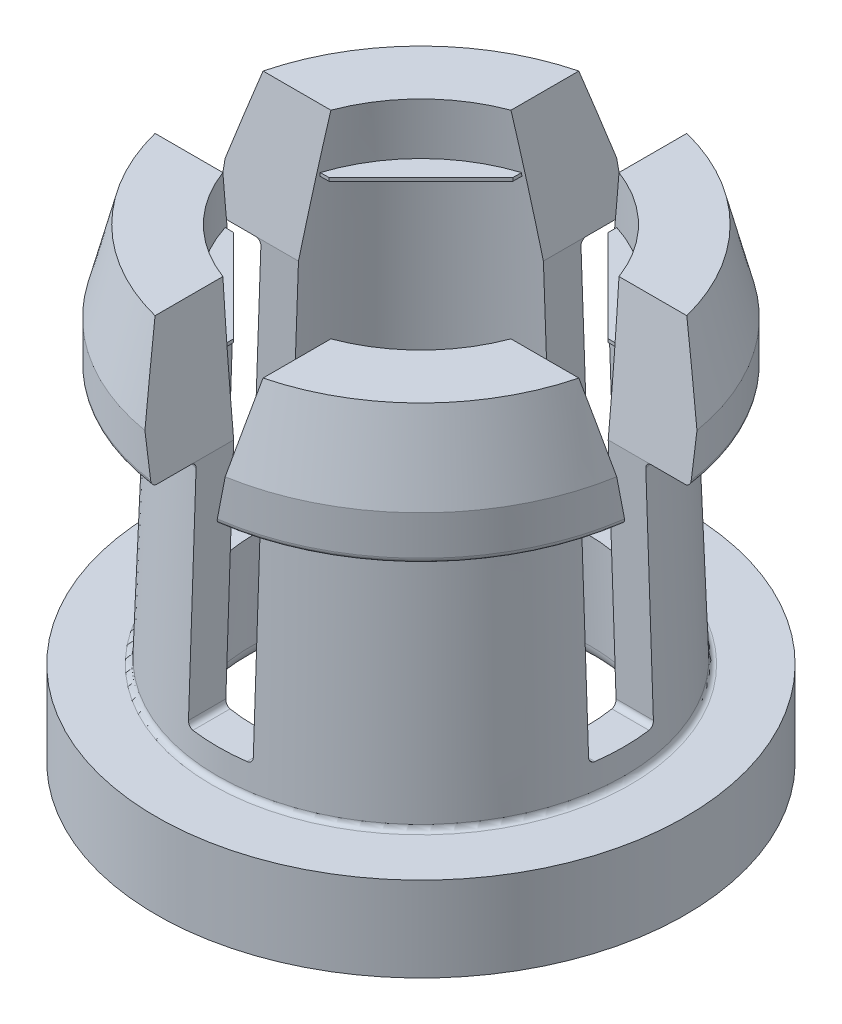
SolidWorks part; units mm, degrees
material "policarbonato"
ref_plane "Alzado" through (0, 0, 0) normal (0, 0, 1) x (1, 0, 0)
ref_plane "Planta" through (0, 0, 0) normal (0, 1, 0) x (1, 0, 0)
ref_plane "Vista lateral" through (0, 0, 0) normal (1, 0, 0) x (0, 0, -1)
sketch "Croquis1" plane through (0, 0, 0) normal (0, 0, 1) x (1, 0, 0)
  line L0 (0, 0) -> (0, 16.8439) construction
  line L2 (3.15, 0) -> (4.9, 0)
  line L3 (4.9, 0) -> (4.9, 1.57)
  line L4 (4.9, 1.57) -> (3.7756, 1.57)
  line L5 (3.7756, 1.57) -> (3.6104, 6.3)
  line L6 (3.6104, 6.3) -> (4.4309, 6.3)
  line L7 (4.4309, 6.3) -> (4.4309, 7.13)
  line L8 (4.4309, 7.13) -> (4.049, 8.62)
  line L9 (4.049, 8.62) -> (2.849, 8.62)
  line L10 (2.849, 8.62) -> (3.15, 0)
  dimension "D1" = 1.75
  dimension "D2" = 3.15
  dimension "D3" = 1.57
  dimension "D4" = 4.73
  dimension "D5" = 8.62
  dimension "D6" = 0.68
  dimension "D7" = 0.83
  dimension "D8" = 1.2
  dimension "D9" = 92
  dimension "D10" = 1.5
revolve "Revolución1" add sketch "Croquis1" angle 360 about L0
sketch "Croquis2" plane through (0, 8.62, 0) normal (0, 1, 0) x (1, 0, 0)
  line L0 (-7.7, 0) -> (-10.6462, 0) construction
  line L1 (0.6, 0.6) -> (0.6, 7.7)
  line L2 (7.7, 0) -> (9.0539, 0) construction
  line L3 (-0.6, 0.6) -> (0.6, -0.6) construction
  line L4 (-0.6, 0.6) -> (-0.6, 7.7)
  line L5 (0.6, 0.6) -> (-0.6, -0.6) construction
  line L6 (-0.6, -7.7) -> (0.6, -7.7)
  line L7 (7.7, 0.6) -> (0.6, 0.6)
  line L8 (-0.6, -7.7) -> (-0.6, -0.6)
  line L9 (-0.6, 7.7) -> (0.6, 7.7)
  line L10 (0.6, -7.7) -> (0.6, -0.6)
  line L11 (-7.7, 0.6) -> (-7.7, -0.6)
  line L12 (-7.7, -0.6) -> (-0.6, -0.6)
  line L13 (7.7, 0.6) -> (7.7, -0.6)
  line L14 (-0.6, 0.6) -> (-7.7, 0.6)
  line L15 (0.6, -0.6) -> (7.7, -0.6)
  point P17 (0, -0.6)
  point P18 (0, 0.6)
  dimension "D3" = 0.6
  dimension "D4" = 0.6
  dimension "D6" = 7.7
extrude "Cortar-Extruir1" cut sketch "Croquis2" against normal blind 6.5
sketch "Croquis3" plane through (0, 0, 0) normal (1, 0, 0) x (0, 0, -1)
  line L0 (-0.6, 6.3) -> (-1, 8.62)
  line L1 (-0.6, 8.62) -> (-4.0043, 8.62) construction
  line L2 (-1, 8.62) -> (1, 8.62)
  line L3 (4.0043, 8.62) -> (0.6, 8.62) construction
  line L4 (1, 8.62) -> (0.6, 6.3)
  line L5 (0.6, 6.3) -> (-0.6, 6.3)
  line L6 (0, 6.3) -> (0, 8.62) construction
  dimension "D1" = 2
extrude "Cortar-Extruir2" cut sketch "Croquis3" against normal through all and the other way through all
sketch "Croquis4" plane through (0, 0, 0) normal (0, 0, 1) x (1, 0, 0)
  line L0 (-0.6, 6.3) -> (-1, 8.62)
  line L1 (-0.6, 8.62) -> (-3.9236, 8.62) construction
  line L2 (-1, 8.62) -> (1, 8.62)
  line L3 (3.9236, 8.62) -> (0.6, 8.62) construction
  line L4 (1, 8.62) -> (0.6, 6.3)
  line L5 (0.6, 6.3) -> (-0.6, 6.3)
  line L6 (0, 6.3) -> (0, 8.62) construction
  dimension "D1" = 2
extrude "Cortar-Extruir3" cut sketch "Croquis4" against normal through all and the other way through all
fillet "Redondeo1" radius 0.1 17 edges at (2.5529, 6.3, -2.5529) (-2.5529, 6.3, -2.5529) (-2.5529, 6.3, 2.5529) (2.5529, 6.3, 2.5529) (0, 1.57, -3.7756) (-3.1331, 6.3, -3.1331) (3.1331, 6.3, -3.1331) (3.1331, 6.3, 3.1331) (-3.1331, 6.3, 3.1331) (-0.6, 2.12, 3.3625) (0.6, 2.12, 3.3625) (-3.3625, 2.12, -0.6) (-3.3625, 2.12, 0.6) (3.3625, 2.12, -0.6) (3.3625, 2.12, 0.6) (-0.6, 2.12, -3.3625) (0.6, 2.12, -3.3625)
sketch "Croquis5" plane through (0, 8.62, 0) normal (0, 1, 0) x (1, 0, 0)
  line L0 (-2.5851, 0.8828) -> (-0.8828, 2.5851)
  line L1 (-0.8732, 3.1601) -> (-1, 3.2956)
  line L2 (-1, 3.9236) -> (-1, 2.6677) construction
  line L3 (-1, 3.2956) -> (-3.2956, 1)
  line L4 (-3.9236, 1) -> (-2.6677, 1) construction
  line L5 (-3.2956, 1) -> (-3.1601, 0.8732)
  line L6 (-2.5851, -0.8828) -> (-0.8828, -2.5851)
  line L7 (-0.8732, -3.1601) -> (-1, -3.2956)
  line L8 (-1, -2.6677) -> (-1, -3.9236) construction
  line L9 (-1, -3.2956) -> (-3.2956, -1)
  line L10 (-3.9236, -1) -> (-2.6677, -1) construction
  line L11 (-3.2956, -1) -> (-3.1601, -0.8732)
  line L12 (0.8828, 2.5851) -> (2.5851, 0.8828)
  line L13 (3.1601, 0.8732) -> (3.2956, 1)
  line L14 (2.6677, 1) -> (3.9236, 1) construction
  line L15 (3.2956, 1) -> (1, 3.2956)
  line L16 (1, 3.9236) -> (1, 2.6677) construction
  line L17 (1, 3.2956) -> (0.8732, 3.1601)
  line L18 (2.5851, -0.8828) -> (0.8828, -2.5851)
  line L19 (0.8732, -3.1601) -> (1, -3.2956)
  line L20 (1, -2.6677) -> (1, -3.9236) construction
  line L21 (1, -3.2956) -> (3.2956, -1)
  line L22 (2.6677, -1) -> (3.9236, -1) construction
  line L23 (3.2956, -1) -> (3.1601, -0.8732)
  line L24 (-0.8828, 2.5851) -> (-0.8732, 3.1601)
  line L25 (-3.1601, 0.8732) -> (-2.5851, 0.8828)
  line L26 (-3.1601, -0.8732) -> (-2.5851, -0.8828)
  line L27 (-0.8828, -2.5851) -> (-0.8732, -3.1601)
  line L28 (0.8828, -2.5851) -> (0.8732, -3.1601)
  line L29 (3.1601, -0.8732) -> (2.5851, -0.8828)
  line L30 (2.5851, 0.8828) -> (3.1601, 0.8732)
  line L31 (0.8732, 3.1601) -> (0.8828, 2.5851)
  point P0 (-2.8679, 0.6)
  point P1 (-0.6, 2.8679)
  point P4 (-2.8679, -0.6)
  point P11 (-0.6, -2.8679)
  point P14 (0.6, 2.8679)
  point P21 (2.8679, 0.6)
  point P24 (2.8679, -0.6)
  point P31 (0.6, -2.8679)
extrude "Saliente-Extruir1" add sketch "Croquis5" against normal blind 0.06 from offset 0.98 offset against normal yes
fillet "Redondeo2" radius 0.3 1 edges at (0, 0, -3.15)
